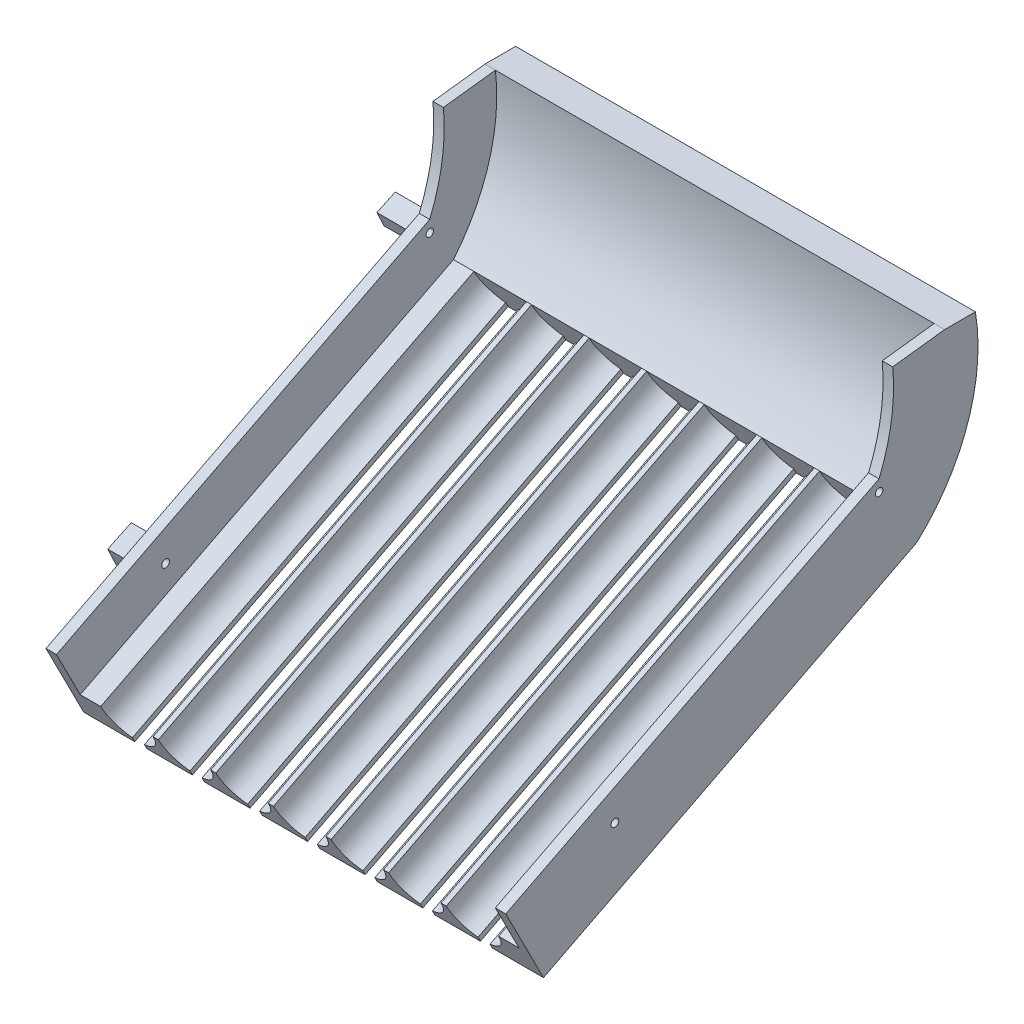
SolidWorks part; units mm, degrees
ref_plane "Front Plane" through (0, 0, 0) normal (0, 0, 1) x (1, 0, 0)
ref_plane "Top Plane" through (0, 0, 0) normal (0, 1, 0) x (1, 0, 0)
ref_plane "Right Plane" through (0, 0, 0) normal (1, 0, 0) x (0, 0, -1)
sketch "Sketch1" plane through (0, 0, 0) normal (1, 0, 0) x (0, 0, -1)
  line L0 (0, 0) -> (1069.2078, 544.7886)
  line L1 (0, 0) -> (-39.9512, 78.4086)
  line L2 (-39.9512, 78.4086) -> (1029.2567, 623.1972)
  line L3 (1029.2567, 623.1972) -> (1069.2078, 544.7886)
  line L6 (1149.2567, 1033.1972) -> (1237.2567, 1033.1972)
  arc A0 (1029.2567, 623.1972) -> (1149.2567, 1033.1972) centre (611.8377, 967.9296) ccw
  arc A1 (1069.2078, 544.7886) -> (1237.2567, 1033.1972) centre (703.3219, 943.7955) ccw
  dimension "D1" = 1200
  dimension "D2" = 88
  dimension "D5" = 88
extrude "Boss-Extrude1" add sketch "Sketch1" along normal blind 1234.9003 and the other way blind 82.1741 contours L3 L2 L1 L0 | L3 A1 L6 A0 region at (0, 311.5986, -514.6283) region at (0, 798.1437, -1158.2532)
sketch "Sketch2" plane through (0, 0, 0) normal (0, -0.454, 0.891) x (1, 0, 0)
  line L0 (576.3631, 88) -> (576.3631, 13) construction
  line L1 (1234.9003, 88) -> (-82.1741, 88) construction
  line L2 (501.3631, 88) -> (651.3631, 88)
  line L3 (559.1585, 0) -> (559.1585, 15)
  line L4 (1234.9003, 0) -> (-82.1741, 0) construction
  line L5 (593.5678, 0) -> (593.5678, 15)
  line L6 (559.1585, 0) -> (593.5678, 0)
  line L7 (658.8631, 88) -> (658.8631, 0) construction
  line L8 (1234.9003, 88) -> (-82.1741, 88) construction
  line L9 (576.3631, 0) -> (576.3631, -197.7637) construction
  line L10 (758.5678, 0) -> (758.5678, 15)
  line L11 (758.5678, 0) -> (724.1585, 0)
  line L12 (724.1585, 0) -> (724.1585, 15)
  line L13 (816.3631, 88) -> (666.3631, 88)
  line L14 (823.8631, 88) -> (823.8631, -20.0766) construction
  line L15 (831.3631, 88) -> (981.3631, 88)
  line L16 (923.5678, 0) -> (923.5678, 15)
  line L17 (889.1585, 0) -> (923.5678, 0)
  line L18 (889.1585, 0) -> (889.1585, 15)
  line L19 (1088.5678, 0) -> (1088.5678, 15)
  line L20 (1088.5678, 0) -> (1054.1585, 0)
  line L21 (1054.1585, 0) -> (1054.1585, 15)
  line L22 (1146.3631, 88) -> (996.3631, 88)
  line L23 (6.3631, 88) -> (156.3631, 88)
  line L24 (98.5678, 0) -> (98.5678, 15)
  line L25 (64.1585, 0) -> (98.5678, 0)
  line L26 (64.1585, 0) -> (64.1585, 15)
  line L27 (263.5678, 0) -> (263.5678, 15)
  line L28 (263.5678, 0) -> (229.1585, 0)
  line L29 (229.1585, 0) -> (229.1585, 15)
  line L30 (321.3631, 88) -> (171.3631, 88)
  line L31 (336.3631, 88) -> (486.3631, 88)
  line L32 (428.5678, 0) -> (428.5678, 15)
  line L33 (394.1585, 0) -> (428.5678, 0)
  line L34 (394.1585, 0) -> (394.1585, 15)
  line L35 (593.5678, 0) -> (593.5678, 15)
  line L36 (559.1585, 0) -> (559.1585, 15)
  arc A0 (501.3631, 88) -> (559.1585, 15) centre (576.3631, 88) ccw
  arc A1 (593.5678, 15) -> (651.3631, 88) centre (576.3631, 88) ccw
  arc A2 (816.3631, 88) -> (758.5678, 15) centre (741.3631, 88) cw
  arc A3 (724.1585, 15) -> (666.3631, 88) centre (741.3631, 88) cw
  arc A4 (923.5678, 15) -> (981.3631, 88) centre (906.3631, 88) ccw
  arc A5 (831.3631, 88) -> (889.1585, 15) centre (906.3631, 88) ccw
  arc A6 (1146.3631, 88) -> (1088.5678, 15) centre (1071.3631, 88) cw
  arc A7 (1054.1585, 15) -> (996.3631, 88) centre (1071.3631, 88) cw
  arc A8 (98.5678, 15) -> (156.3631, 88) centre (81.3631, 88) ccw
  arc A9 (6.3631, 88) -> (64.1585, 15) centre (81.3631, 88) ccw
  arc A10 (321.3631, 88) -> (263.5678, 15) centre (246.3631, 88) cw
  arc A11 (229.1585, 15) -> (171.3631, 88) centre (246.3631, 88) cw
  arc A12 (428.5678, 15) -> (486.3631, 88) centre (411.3631, 88) ccw
  arc A13 (336.3631, 88) -> (394.1585, 15) centre (411.3631, 88) ccw
  arc A14 (651.3631, 88) -> (593.5678, 15) centre (576.3631, 88) cw
  arc A15 (559.1585, 15) -> (501.3631, 88) centre (576.3631, 88) cw
  line M30 (-82.1741, 0) -> (1234.9003, 0)
  line M32 (1234.9003, 88) -> (-82.1741, 88)
  dimension "D1" = 150
  dimension "D2" = 15
  dimension "D3" = 7.5
  dimension "D4" = 7.5
extrude "Cut-Extrude1" cut sketch "Sketch2" against normal blind 1200 contours A9 L26 L24 A8 M32 M30 | A11 L29 L27 A10 M30 M32 | A13 L34 L32 A12 M32 M30 | L5 A1 A0 L3 M32 M30 | A3 L12 L10 A2 M30 M32 | A5 L18 L16 A4 M32 M30 | A7 L21 L19 A6 M30 M32 region at (576.3631, 47.8267, 24.3689) region at (411.3631, 47.8267, 24.3689) region at (741.3631, 47.8267, 24.3689) region at (246.3631, 47.8267, 24.3689) region at (906.3631, 47.8267, 24.3689) region at (81.3631, 47.8267, 24.3689) region at (1071.3631, 47.8267, 24.3689)
sketch "Sketch3" plane through (1234.9003, 0, 0) normal (1, 0, 0) x (0, 0, -1)
  line L0 (-39.9512, 78.4086) -> (-108.0497, 212.0596)
  line L2 (-39.9512, 78.4086) -> (1029.2567, 623.1972)
  line L3 (1029.2567, 623.1972) -> (961.1581, 756.8482)
  line L4 (-108.0497, 212.0596) -> (961.1581, 756.8482)
  dimension "D1" = 150
  dimension "D2" = 150
extrude "Boss-Extrude2" add sketch "Sketch3" against normal blind 30
sketch "Sketch4" plane through (-82.1741, 0, 0) normal (-1, 0, 0) x (0, 0, 1)
  line L0 (-1029.2567, 623.1972) -> (-961.1581, 756.8482)
  line L1 (-1029.2567, 623.1972) -> (-961.1581, 756.8482) construction
sketch "Sketch6" plane through (-82.1741, 0, 0) normal (-1, 0, 0) x (0, 0, 1)
  line L0 (-1029.2567, 623.1972) -> (-961.1581, 756.8482)
  line L1 (-961.1581, 756.8482) -> (108.0497, 212.0596)
  line L2 (108.0497, 212.0596) -> (39.9512, 78.4086)
  line L3 (39.9512, 78.4086) -> (-1029.2567, 623.1972)
extrude "Boss-Extrude3" add sketch "Sketch6" against normal blind 30
sketch "Sketch9" plane through (1234.9003, 0, 0) normal (1, 0, 0) x (0, 0, -1)
  line L0 (1149.2567, 1033.1972) -> (1000.3508, 1015.1131)
  line L1 (961.1581, 756.8482) -> (1029.2567, 623.1972)
  arc A0 (1029.2567, 623.1972) -> (1149.2567, 1033.1972) centre (611.8377, 967.9296) ccw
  arc A1 (1000.3508, 1015.1131) -> (961.1581, 756.8482) centre (461.3255, 964.8059) cw
  dimension "D1" = 150
extrude "Boss-Extrude4" add sketch "Sketch9" against normal blind 30
sketch "Sketch10" plane through (-82.1741, 0, 0) normal (-1, 0, 0) x (0, 0, 1)
  line L0 (-1029.2567, 623.1972) -> (-961.1581, 756.8482)
  line L1 (-1149.2567, 1033.1972) -> (-1000.3508, 1015.1131)
  arc A0 (-1000.3508, 1015.1131) -> (-961.1581, 756.8482) centre (-461.3255, 964.8059) ccw
  arc A1 (-1149.2567, 1033.1972) -> (-1029.2567, 623.1972) centre (-611.8377, 967.9296) ccw
extrude "Boss-Extrude5" add sketch "Sketch10" against normal blind 30
sketch "Sketch11" plane through (-82.1741, 0, 0) normal (-1, 0, 0) x (0, 0, 1)
  line L0 (-982.2261, 754.4909) -> (-929.7679, 729.6423)
  line L1 (-929.7679, 729.6423) -> (-950.2314, 686.4414)
  line L2 (-950.2314, 686.4414) -> (-1002.6897, 711.2901)
  line L3 (-1002.6897, 711.2901) -> (-982.2261, 754.4909)
  line L4 (-226.1333, 312.1036) -> (-158.8079, 280.2126)
  line L5 (-158.8079, 280.2126) -> (-183.7008, 227.6609)
  line L6 (-183.7008, 227.6609) -> (-251.9199, 257.6652)
  line L7 (454.4739, 257.6652) -> (164.4739, 257.6652) construction
  line L8 (-251.9199, 257.6652) -> (-226.1333, 312.1036)
extrude "Boss-Extrude6" add sketch "Sketch11" along normal blind 90
sketch "Sketch12" plane through (1234.9003, 0, 0) normal (1, 0, 0) x (0, 0, -1)
  circle A0 centre (204.629, 281.8388) radius 11.0904
  circle A1 centre (961.3896, 723.7123) radius 10.7496
extrude "Cut-Extrude2" cut sketch "Sketch12" against normal blind 1710 and the other way blind 1710
